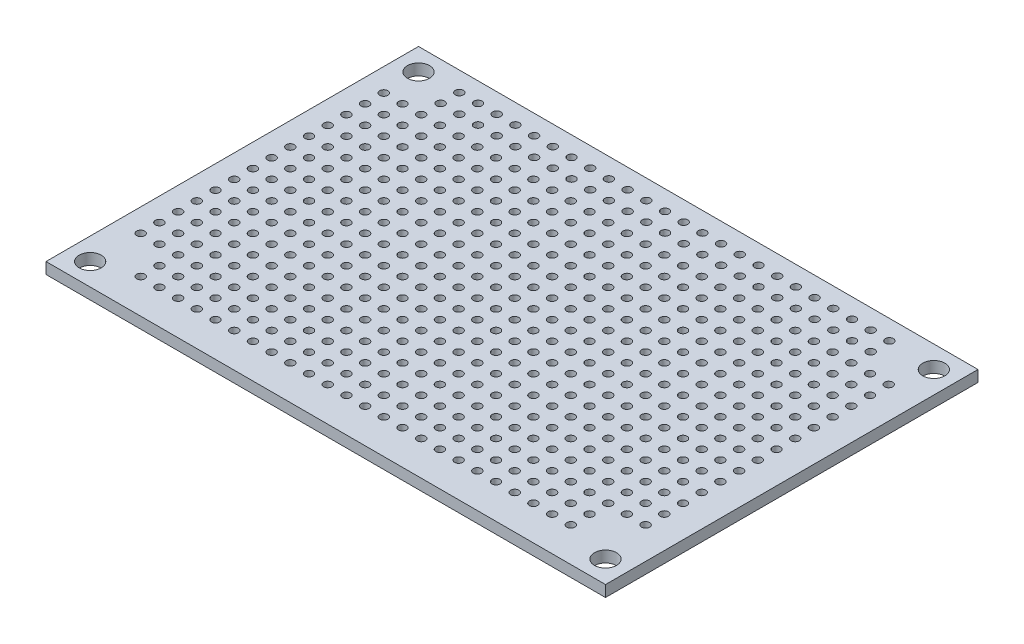
SolidWorks part; units mm, degrees
ref_plane "Front Plane" through (0, 0, 0) normal (0, 0, 1) x (1, 0, 0)
ref_plane "Top Plane" through (0, 0, 0) normal (0, 1, 0) x (1, 0, 0)
ref_plane "Right Plane" through (0, 0, 0) normal (1, 0, 0) x (0, 0, -1)
sketch "Sketch1" plane through (0, 0, 0) normal (0, 1, 0) x (1, 0, 0)
  line L0 (0, 22.3) -> (0, -22.3) construction
  line L1 (-38, -25.3) -> (38, -25.3)
  line L2 (-38, -25.3) -> (-38, 25.3)
  line L3 (-38, 25.3) -> (38, 25.3)
  line L4 (38, -25.3) -> (38, 25.3)
  line L5 (-38, -25.3) -> (38, 25.3) construction
  line L6 (-38, 25.3) -> (38, -25.3) construction
  line L7 (-35, 22.3) -> (35, 22.3) construction
  line L8 (-35, 22.3) -> (-35, -22.3) construction
  line L9 (-35, -22.3) -> (35, -22.3) construction
  line L10 (35, 22.3) -> (35, -22.3) construction
  circle A0 centre (35, 22.3) radius 1.5
  circle A1 centre (35, -22.3) radius 1.5
  circle A2 centre (-35, -22.3) radius 1.5
  circle A3 centre (-35, 22.3) radius 1.5
  point P0 (0, 0)
  dimension "D4" = 3
  dimension "D1" = 76
  dimension "D2" = 50.6
  dimension "D3" = 44.6
  dimension "D5" = 70
extrude "Boss-Extrude1" add sketch "Sketch1" along normal blind 1.53
sketch "Sketch2" plane through (0, 1.53, 0) normal (0, 1, 0) x (1, 0, 0)
  line L0 (-34.8792, 17.4666) -> (-32.3392, 17.4666) construction
  line L1 (-29.7992, 20.1014) -> (-29.7992, 17.5614) construction
  line L2 (-29.7992, -15.5534) -> (-29.7992, -18.0934) construction
  circle A0 centre (-34.8792, 17.4666) radius 0.55
  circle A1 centre (-32.3392, 17.4666) radius 0.55
  circle A2 centre (-29.7992, 17.4666) radius 0.55
  circle A3 centre (-27.2592, 17.4666) radius 0.55
  circle A4 centre (-24.7192, 17.4666) radius 0.55
  circle A5 centre (-22.1792, 17.4666) radius 0.55
  circle A6 centre (-19.6392, 17.4666) radius 0.55
  circle A7 centre (-17.0992, 17.4666) radius 0.55
  circle A8 centre (-14.5592, 17.4666) radius 0.55
  circle A9 centre (-12.0192, 17.4666) radius 0.55
  circle A10 centre (-9.4792, 17.4666) radius 0.55
  circle A11 centre (-6.9392, 17.4666) radius 0.55
  circle A12 centre (-4.3992, 17.4666) radius 0.55
  circle A13 centre (-1.8592, 17.4666) radius 0.55
  circle A14 centre (0.6808, 17.4666) radius 0.55
  circle A15 centre (3.2208, 17.4666) radius 0.55
  circle A16 centre (5.7608, 17.4666) radius 0.55
  circle A17 centre (8.3008, 17.4666) radius 0.55
  circle A18 centre (10.8408, 17.4666) radius 0.55
  circle A19 centre (13.3808, 17.4666) radius 0.55
  circle A20 centre (15.9208, 17.4666) radius 0.55
  circle A21 centre (18.4608, 17.4666) radius 0.55
  circle A22 centre (21.0008, 17.4666) radius 0.55
  circle A23 centre (23.5408, 17.4666) radius 0.55
  circle A24 centre (26.0808, 17.4666) radius 0.55
  circle A25 centre (28.6208, 17.4666) radius 0.55
  circle A26 centre (31.1608, 17.4666) radius 0.55
  circle A27 centre (33.7008, 17.4666) radius 0.55
  circle A28 centre (-32.3392, 14.9266) radius 0.55
  circle A29 centre (-29.7992, 14.9266) radius 0.55
  circle A30 centre (-27.2592, 14.9266) radius 0.55
  circle A31 centre (-24.7192, 14.9266) radius 0.55
  circle A32 centre (-22.1792, 14.9266) radius 0.55
  circle A33 centre (-19.6392, 14.9266) radius 0.55
  circle A34 centre (-17.0992, 14.9266) radius 0.55
  circle A35 centre (-14.5592, 14.9266) radius 0.55
  circle A36 centre (-12.0192, 14.9266) radius 0.55
  circle A37 centre (-9.4792, 14.9266) radius 0.55
  circle A38 centre (-6.9392, 14.9266) radius 0.55
  circle A39 centre (-4.3992, 14.9266) radius 0.55
  circle A40 centre (-1.8592, 14.9266) radius 0.55
  circle A41 centre (0.6808, 14.9266) radius 0.55
  circle A42 centre (3.2208, 14.9266) radius 0.55
  circle A43 centre (5.7608, 14.9266) radius 0.55
  circle A44 centre (8.3008, 14.9266) radius 0.55
  circle A45 centre (10.8408, 14.9266) radius 0.55
  circle A46 centre (13.3808, 14.9266) radius 0.55
  circle A47 centre (15.9208, 14.9266) radius 0.55
  circle A48 centre (18.4608, 14.9266) radius 0.55
  circle A49 centre (21.0008, 14.9266) radius 0.55
  circle A50 centre (23.5408, 14.9266) radius 0.55
  circle A51 centre (26.0808, 14.9266) radius 0.55
  circle A52 centre (28.6208, 14.9266) radius 0.55
  circle A53 centre (31.1608, 14.9266) radius 0.55
  circle A54 centre (33.7008, 14.9266) radius 0.55
  circle A55 centre (-32.3392, 12.3866) radius 0.55
  circle A56 centre (-29.7992, 12.3866) radius 0.55
  circle A57 centre (-27.2592, 12.3866) radius 0.55
  circle A58 centre (-24.7192, 12.3866) radius 0.55
  circle A59 centre (-22.1792, 12.3866) radius 0.55
  circle A60 centre (-19.6392, 12.3866) radius 0.55
  circle A61 centre (-17.0992, 12.3866) radius 0.55
  circle A62 centre (-14.5592, 12.3866) radius 0.55
  circle A63 centre (-12.0192, 12.3866) radius 0.55
  circle A64 centre (-9.4792, 12.3866) radius 0.55
  circle A65 centre (-6.9392, 12.3866) radius 0.55
  circle A66 centre (-4.3992, 12.3866) radius 0.55
  circle A67 centre (-1.8592, 12.3866) radius 0.55
  circle A68 centre (0.6808, 12.3866) radius 0.55
  circle A69 centre (3.2208, 12.3866) radius 0.55
  circle A70 centre (5.7608, 12.3866) radius 0.55
  circle A71 centre (8.3008, 12.3866) radius 0.55
  circle A72 centre (10.8408, 12.3866) radius 0.55
  circle A73 centre (13.3808, 12.3866) radius 0.55
  circle A74 centre (15.9208, 12.3866) radius 0.55
  circle A75 centre (18.4608, 12.3866) radius 0.55
  circle A76 centre (21.0008, 12.3866) radius 0.55
  circle A77 centre (23.5408, 12.3866) radius 0.55
  circle A78 centre (26.0808, 12.3866) radius 0.55
  circle A79 centre (28.6208, 12.3866) radius 0.55
  circle A80 centre (31.1608, 12.3866) radius 0.55
  circle A81 centre (33.7008, 12.3866) radius 0.55
  circle A82 centre (-32.3392, 9.8466) radius 0.55
  circle A83 centre (-29.7992, 9.8466) radius 0.55
  circle A84 centre (-27.2592, 9.8466) radius 0.55
  circle A85 centre (-24.7192, 9.8466) radius 0.55
  circle A86 centre (-22.1792, 9.8466) radius 0.55
  circle A87 centre (-19.6392, 9.8466) radius 0.55
  circle A88 centre (-17.0992, 9.8466) radius 0.55
  circle A89 centre (-14.5592, 9.8466) radius 0.55
  circle A90 centre (-12.0192, 9.8466) radius 0.55
  circle A91 centre (-9.4792, 9.8466) radius 0.55
  circle A92 centre (-6.9392, 9.8466) radius 0.55
  circle A93 centre (-4.3992, 9.8466) radius 0.55
  circle A94 centre (-1.8592, 9.8466) radius 0.55
  circle A95 centre (0.6808, 9.8466) radius 0.55
  circle A96 centre (3.2208, 9.8466) radius 0.55
  circle A97 centre (5.7608, 9.8466) radius 0.55
  circle A98 centre (8.3008, 9.8466) radius 0.55
  circle A99 centre (10.8408, 9.8466) radius 0.55
  circle A100 centre (13.3808, 9.8466) radius 0.55
  circle A101 centre (15.9208, 9.8466) radius 0.55
  circle A102 centre (18.4608, 9.8466) radius 0.55
  circle A103 centre (21.0008, 9.8466) radius 0.55
  circle A104 centre (23.5408, 9.8466) radius 0.55
  circle A105 centre (26.0808, 9.8466) radius 0.55
  circle A106 centre (28.6208, 9.8466) radius 0.55
  circle A107 centre (31.1608, 9.8466) radius 0.55
  circle A108 centre (33.7008, 9.8466) radius 0.55
  circle A109 centre (-32.3392, 7.3066) radius 0.55
  circle A110 centre (-29.7992, 7.3066) radius 0.55
  circle A111 centre (-27.2592, 7.3066) radius 0.55
  circle A112 centre (-24.7192, 7.3066) radius 0.55
  circle A113 centre (-22.1792, 7.3066) radius 0.55
  circle A114 centre (-19.6392, 7.3066) radius 0.55
  circle A115 centre (-17.0992, 7.3066) radius 0.55
  circle A116 centre (-14.5592, 7.3066) radius 0.55
  circle A117 centre (-12.0192, 7.3066) radius 0.55
  circle A118 centre (-9.4792, 7.3066) radius 0.55
  circle A119 centre (-6.9392, 7.3066) radius 0.55
  circle A120 centre (-4.3992, 7.3066) radius 0.55
  circle A121 centre (-1.8592, 7.3066) radius 0.55
  circle A122 centre (0.6808, 7.3066) radius 0.55
  circle A123 centre (3.2208, 7.3066) radius 0.55
  circle A124 centre (5.7608, 7.3066) radius 0.55
  circle A125 centre (8.3008, 7.3066) radius 0.55
  circle A126 centre (10.8408, 7.3066) radius 0.55
  circle A127 centre (13.3808, 7.3066) radius 0.55
  circle A128 centre (15.9208, 7.3066) radius 0.55
  circle A129 centre (18.4608, 7.3066) radius 0.55
  circle A130 centre (21.0008, 7.3066) radius 0.55
  circle A131 centre (23.5408, 7.3066) radius 0.55
  circle A132 centre (26.0808, 7.3066) radius 0.55
  circle A133 centre (28.6208, 7.3066) radius 0.55
  circle A134 centre (31.1608, 7.3066) radius 0.55
  circle A135 centre (33.7008, 7.3066) radius 0.55
  circle A136 centre (-32.3392, 4.7666) radius 0.55
  circle A137 centre (-29.7992, 4.7666) radius 0.55
  circle A138 centre (-27.2592, 4.7666) radius 0.55
  circle A139 centre (-24.7192, 4.7666) radius 0.55
  circle A140 centre (-22.1792, 4.7666) radius 0.55
  circle A141 centre (-19.6392, 4.7666) radius 0.55
  circle A142 centre (-17.0992, 4.7666) radius 0.55
  circle A143 centre (-14.5592, 4.7666) radius 0.55
  circle A144 centre (-12.0192, 4.7666) radius 0.55
  circle A145 centre (-9.4792, 4.7666) radius 0.55
  circle A146 centre (-6.9392, 4.7666) radius 0.55
  circle A147 centre (-4.3992, 4.7666) radius 0.55
  circle A148 centre (-1.8592, 4.7666) radius 0.55
  circle A149 centre (0.6808, 4.7666) radius 0.55
  circle A150 centre (3.2208, 4.7666) radius 0.55
  circle A151 centre (5.7608, 4.7666) radius 0.55
  circle A152 centre (8.3008, 4.7666) radius 0.55
  circle A153 centre (10.8408, 4.7666) radius 0.55
  circle A154 centre (13.3808, 4.7666) radius 0.55
  circle A155 centre (15.9208, 4.7666) radius 0.55
  circle A156 centre (18.4608, 4.7666) radius 0.55
  circle A157 centre (21.0008, 4.7666) radius 0.55
  circle A158 centre (23.5408, 4.7666) radius 0.55
  circle A159 centre (26.0808, 4.7666) radius 0.55
  circle A160 centre (28.6208, 4.7666) radius 0.55
  circle A161 centre (31.1608, 4.7666) radius 0.55
  circle A162 centre (33.7008, 4.7666) radius 0.55
  circle A163 centre (-32.3392, 2.2266) radius 0.55
  circle A164 centre (-29.7992, 2.2266) radius 0.55
  circle A165 centre (-27.2592, 2.2266) radius 0.55
  circle A166 centre (-24.7192, 2.2266) radius 0.55
  circle A167 centre (-22.1792, 2.2266) radius 0.55
  circle A168 centre (-19.6392, 2.2266) radius 0.55
  circle A169 centre (-17.0992, 2.2266) radius 0.55
  circle A170 centre (-14.5592, 2.2266) radius 0.55
  circle A171 centre (-12.0192, 2.2266) radius 0.55
  circle A172 centre (-9.4792, 2.2266) radius 0.55
  circle A173 centre (-6.9392, 2.2266) radius 0.55
  circle A174 centre (-4.3992, 2.2266) radius 0.55
  circle A175 centre (-1.8592, 2.2266) radius 0.55
  circle A176 centre (0.6808, 2.2266) radius 0.55
  circle A177 centre (3.2208, 2.2266) radius 0.55
  circle A178 centre (5.7608, 2.2266) radius 0.55
  circle A179 centre (8.3008, 2.2266) radius 0.55
  circle A180 centre (10.8408, 2.2266) radius 0.55
  circle A181 centre (13.3808, 2.2266) radius 0.55
  circle A182 centre (15.9208, 2.2266) radius 0.55
  circle A183 centre (18.4608, 2.2266) radius 0.55
  circle A184 centre (21.0008, 2.2266) radius 0.55
  circle A185 centre (23.5408, 2.2266) radius 0.55
  circle A186 centre (26.0808, 2.2266) radius 0.55
  circle A187 centre (28.6208, 2.2266) radius 0.55
  circle A188 centre (31.1608, 2.2266) radius 0.55
  circle A189 centre (33.7008, 2.2266) radius 0.55
  circle A190 centre (-32.3392, -0.3134) radius 0.55
  circle A191 centre (-29.7992, -0.3134) radius 0.55
  circle A192 centre (-27.2592, -0.3134) radius 0.55
  circle A193 centre (-24.7192, -0.3134) radius 0.55
  circle A194 centre (-22.1792, -0.3134) radius 0.55
  circle A195 centre (-19.6392, -0.3134) radius 0.55
  circle A196 centre (-17.0992, -0.3134) radius 0.55
  circle A197 centre (-14.5592, -0.3134) radius 0.55
  circle A198 centre (-12.0192, -0.3134) radius 0.55
  circle A199 centre (-9.4792, -0.3134) radius 0.55
  circle A200 centre (-6.9392, -0.3134) radius 0.55
  circle A201 centre (-4.3992, -0.3134) radius 0.55
  circle A202 centre (-1.8592, -0.3134) radius 0.55
  circle A203 centre (0.6808, -0.3134) radius 0.55
  circle A204 centre (3.2208, -0.3134) radius 0.55
  circle A205 centre (5.7608, -0.3134) radius 0.55
  circle A206 centre (8.3008, -0.3134) radius 0.55
  circle A207 centre (10.8408, -0.3134) radius 0.55
  circle A208 centre (13.3808, -0.3134) radius 0.55
  circle A209 centre (15.9208, -0.3134) radius 0.55
  circle A210 centre (18.4608, -0.3134) radius 0.55
  circle A211 centre (21.0008, -0.3134) radius 0.55
  circle A212 centre (23.5408, -0.3134) radius 0.55
  circle A213 centre (26.0808, -0.3134) radius 0.55
  circle A214 centre (28.6208, -0.3134) radius 0.55
  circle A215 centre (31.1608, -0.3134) radius 0.55
  circle A216 centre (33.7008, -0.3134) radius 0.55
  circle A217 centre (-32.3392, -2.8534) radius 0.55
  circle A218 centre (-29.7992, -2.8534) radius 0.55
  circle A219 centre (-27.2592, -2.8534) radius 0.55
  circle A220 centre (-24.7192, -2.8534) radius 0.55
  circle A221 centre (-22.1792, -2.8534) radius 0.55
  circle A222 centre (-19.6392, -2.8534) radius 0.55
  circle A223 centre (-17.0992, -2.8534) radius 0.55
  circle A224 centre (-14.5592, -2.8534) radius 0.55
  circle A225 centre (-12.0192, -2.8534) radius 0.55
  circle A226 centre (-9.4792, -2.8534) radius 0.55
  circle A227 centre (-6.9392, -2.8534) radius 0.55
  circle A228 centre (-4.3992, -2.8534) radius 0.55
  circle A229 centre (-1.8592, -2.8534) radius 0.55
  circle A230 centre (0.6808, -2.8534) radius 0.55
  circle A231 centre (3.2208, -2.8534) radius 0.55
  circle A232 centre (5.7608, -2.8534) radius 0.55
  circle A233 centre (8.3008, -2.8534) radius 0.55
  circle A234 centre (10.8408, -2.8534) radius 0.55
  circle A235 centre (13.3808, -2.8534) radius 0.55
  circle A236 centre (15.9208, -2.8534) radius 0.55
  circle A237 centre (18.4608, -2.8534) radius 0.55
  circle A238 centre (21.0008, -2.8534) radius 0.55
  circle A239 centre (23.5408, -2.8534) radius 0.55
  circle A240 centre (26.0808, -2.8534) radius 0.55
  circle A241 centre (28.6208, -2.8534) radius 0.55
  circle A242 centre (31.1608, -2.8534) radius 0.55
  circle A243 centre (33.7008, -2.8534) radius 0.55
  circle A244 centre (-32.3392, -5.3934) radius 0.55
  circle A245 centre (-29.7992, -5.3934) radius 0.55
  circle A246 centre (-27.2592, -5.3934) radius 0.55
  circle A247 centre (-24.7192, -5.3934) radius 0.55
  circle A248 centre (-22.1792, -5.3934) radius 0.55
  circle A249 centre (-19.6392, -5.3934) radius 0.55
  circle A250 centre (-17.0992, -5.3934) radius 0.55
  circle A251 centre (-14.5592, -5.3934) radius 0.55
  circle A252 centre (-12.0192, -5.3934) radius 0.55
  circle A253 centre (-9.4792, -5.3934) radius 0.55
  circle A254 centre (-6.9392, -5.3934) radius 0.55
  circle A255 centre (-4.3992, -5.3934) radius 0.55
  circle A256 centre (-1.8592, -5.3934) radius 0.55
  circle A257 centre (0.6808, -5.3934) radius 0.55
  circle A258 centre (3.2208, -5.3934) radius 0.55
  circle A259 centre (5.7608, -5.3934) radius 0.55
  circle A260 centre (8.3008, -5.3934) radius 0.55
  circle A261 centre (10.8408, -5.3934) radius 0.55
  circle A262 centre (13.3808, -5.3934) radius 0.55
  circle A263 centre (15.9208, -5.3934) radius 0.55
  circle A264 centre (18.4608, -5.3934) radius 0.55
  circle A265 centre (21.0008, -5.3934) radius 0.55
  circle A266 centre (23.5408, -5.3934) radius 0.55
  circle A267 centre (26.0808, -5.3934) radius 0.55
  circle A268 centre (28.6208, -5.3934) radius 0.55
  circle A269 centre (31.1608, -5.3934) radius 0.55
  circle A270 centre (33.7008, -5.3934) radius 0.55
  circle A271 centre (-32.3392, -7.9334) radius 0.55
  circle A272 centre (-29.7992, -7.9334) radius 0.55
  circle A273 centre (-27.2592, -7.9334) radius 0.55
  circle A274 centre (-24.7192, -7.9334) radius 0.55
  circle A275 centre (-22.1792, -7.9334) radius 0.55
  circle A276 centre (-19.6392, -7.9334) radius 0.55
  circle A277 centre (-17.0992, -7.9334) radius 0.55
  circle A278 centre (-14.5592, -7.9334) radius 0.55
  circle A279 centre (-12.0192, -7.9334) radius 0.55
  circle A280 centre (-9.4792, -7.9334) radius 0.55
  circle A281 centre (-6.9392, -7.9334) radius 0.55
  circle A282 centre (-4.3992, -7.9334) radius 0.55
  circle A283 centre (-1.8592, -7.9334) radius 0.55
  circle A284 centre (0.6808, -7.9334) radius 0.55
  circle A285 centre (3.2208, -7.9334) radius 0.55
  circle A286 centre (5.7608, -7.9334) radius 0.55
  circle A287 centre (8.3008, -7.9334) radius 0.55
  circle A288 centre (10.8408, -7.9334) radius 0.55
  circle A289 centre (13.3808, -7.9334) radius 0.55
  circle A290 centre (15.9208, -7.9334) radius 0.55
  circle A291 centre (18.4608, -7.9334) radius 0.55
  circle A292 centre (21.0008, -7.9334) radius 0.55
  circle A293 centre (23.5408, -7.9334) radius 0.55
  circle A294 centre (26.0808, -7.9334) radius 0.55
  circle A295 centre (28.6208, -7.9334) radius 0.55
  circle A296 centre (31.1608, -7.9334) radius 0.55
  circle A297 centre (33.7008, -7.9334) radius 0.55
  circle A298 centre (-32.3392, -10.4734) radius 0.55
  circle A299 centre (-29.7992, -10.4734) radius 0.55
  circle A300 centre (-27.2592, -10.4734) radius 0.55
  circle A301 centre (-24.7192, -10.4734) radius 0.55
  circle A302 centre (-22.1792, -10.4734) radius 0.55
  circle A303 centre (-19.6392, -10.4734) radius 0.55
  circle A304 centre (-17.0992, -10.4734) radius 0.55
  circle A305 centre (-14.5592, -10.4734) radius 0.55
  circle A306 centre (-12.0192, -10.4734) radius 0.55
  circle A307 centre (-9.4792, -10.4734) radius 0.55
  circle A308 centre (-6.9392, -10.4734) radius 0.55
  circle A309 centre (-4.3992, -10.4734) radius 0.55
  circle A310 centre (-1.8592, -10.4734) radius 0.55
  circle A311 centre (0.6808, -10.4734) radius 0.55
  circle A312 centre (3.2208, -10.4734) radius 0.55
  circle A313 centre (5.7608, -10.4734) radius 0.55
  circle A314 centre (8.3008, -10.4734) radius 0.55
  circle A315 centre (10.8408, -10.4734) radius 0.55
  circle A316 centre (13.3808, -10.4734) radius 0.55
  circle A317 centre (15.9208, -10.4734) radius 0.55
  circle A318 centre (18.4608, -10.4734) radius 0.55
  circle A319 centre (21.0008, -10.4734) radius 0.55
  circle A320 centre (23.5408, -10.4734) radius 0.55
  circle A321 centre (26.0808, -10.4734) radius 0.55
  circle A322 centre (28.6208, -10.4734) radius 0.55
  circle A323 centre (31.1608, -10.4734) radius 0.55
  circle A324 centre (33.7008, -10.4734) radius 0.55
  circle A325 centre (-32.3392, -13.0134) radius 0.55
  circle A326 centre (-29.7992, -13.0134) radius 0.55
  circle A327 centre (-27.2592, -13.0134) radius 0.55
  circle A328 centre (-24.7192, -13.0134) radius 0.55
  circle A329 centre (-22.1792, -13.0134) radius 0.55
  circle A330 centre (-19.6392, -13.0134) radius 0.55
  circle A331 centre (-17.0992, -13.0134) radius 0.55
  circle A332 centre (-14.5592, -13.0134) radius 0.55
  circle A333 centre (-12.0192, -13.0134) radius 0.55
  circle A334 centre (-9.4792, -13.0134) radius 0.55
  circle A335 centre (-6.9392, -13.0134) radius 0.55
  circle A336 centre (-4.3992, -13.0134) radius 0.55
  circle A337 centre (-1.8592, -13.0134) radius 0.55
  circle A338 centre (0.6808, -13.0134) radius 0.55
  circle A339 centre (3.2208, -13.0134) radius 0.55
  circle A340 centre (5.7608, -13.0134) radius 0.55
  circle A341 centre (8.3008, -13.0134) radius 0.55
  circle A342 centre (10.8408, -13.0134) radius 0.55
  circle A343 centre (13.3808, -13.0134) radius 0.55
  circle A344 centre (15.9208, -13.0134) radius 0.55
  circle A345 centre (18.4608, -13.0134) radius 0.55
  circle A346 centre (21.0008, -13.0134) radius 0.55
  circle A347 centre (23.5408, -13.0134) radius 0.55
  circle A348 centre (26.0808, -13.0134) radius 0.55
  circle A349 centre (28.6208, -13.0134) radius 0.55
  circle A350 centre (31.1608, -13.0134) radius 0.55
  circle A351 centre (33.7008, -13.0134) radius 0.55
  circle A352 centre (-32.3392, -15.5534) radius 0.55
  circle A353 centre (-29.7992, -15.5534) radius 0.55
  circle A354 centre (-27.2592, -15.5534) radius 0.55
  circle A355 centre (-24.7192, -15.5534) radius 0.55
  circle A356 centre (-22.1792, -15.5534) radius 0.55
  circle A357 centre (-19.6392, -15.5534) radius 0.55
  circle A358 centre (-17.0992, -15.5534) radius 0.55
  circle A359 centre (-14.5592, -15.5534) radius 0.55
  circle A360 centre (-12.0192, -15.5534) radius 0.55
  circle A361 centre (-9.4792, -15.5534) radius 0.55
  circle A362 centre (-6.9392, -15.5534) radius 0.55
  circle A363 centre (-4.3992, -15.5534) radius 0.55
  circle A364 centre (-1.8592, -15.5534) radius 0.55
  circle A365 centre (0.6808, -15.5534) radius 0.55
  circle A366 centre (3.2208, -15.5534) radius 0.55
  circle A367 centre (5.7608, -15.5534) radius 0.55
  circle A368 centre (8.3008, -15.5534) radius 0.55
  circle A369 centre (10.8408, -15.5534) radius 0.55
  circle A370 centre (13.3808, -15.5534) radius 0.55
  circle A371 centre (15.9208, -15.5534) radius 0.55
  circle A372 centre (18.4608, -15.5534) radius 0.55
  circle A373 centre (21.0008, -15.5534) radius 0.55
  circle A374 centre (23.5408, -15.5534) radius 0.55
  circle A375 centre (26.0808, -15.5534) radius 0.55
  circle A376 centre (28.6208, -15.5534) radius 0.55
  circle A377 centre (31.1608, -15.5534) radius 0.55
  circle A378 centre (33.7008, -15.5534) radius 0.55
  circle A379 centre (-34.8792, 14.9266) radius 0.55
  circle A380 centre (-34.8792, 12.3866) radius 0.55
  circle A381 centre (-34.8792, 9.8466) radius 0.55
  circle A382 centre (-34.8792, 7.3066) radius 0.55
  circle A383 centre (-34.8792, 4.7666) radius 0.55
  circle A384 centre (-34.8792, 2.2266) radius 0.55
  circle A385 centre (-34.8792, -0.3134) radius 0.55
  circle A386 centre (-34.8792, -2.8534) radius 0.55
  circle A387 centre (-34.8792, -5.3934) radius 0.55
  circle A388 centre (-34.8792, -7.9334) radius 0.55
  circle A389 centre (-34.8792, -10.4734) radius 0.55
  circle A390 centre (-34.8792, -13.0134) radius 0.55
  circle A391 centre (-34.8792, -15.5534) radius 0.55
  circle A392 centre (-29.7992, 20.1014) radius 0.55
  circle A393 centre (-27.2592, 20.1014) radius 0.55
  circle A394 centre (-24.7192, 20.1014) radius 0.55
  circle A395 centre (-22.1792, 20.1014) radius 0.55
  circle A396 centre (-19.6392, 20.1014) radius 0.55
  circle A397 centre (-17.0992, 20.1014) radius 0.55
  circle A398 centre (-14.5592, 20.1014) radius 0.55
  circle A399 centre (-12.0192, 20.1014) radius 0.55
  circle A400 centre (-9.4792, 20.1014) radius 0.55
  circle A401 centre (-6.9392, 20.1014) radius 0.55
  circle A402 centre (-4.3992, 20.1014) radius 0.55
  circle A403 centre (-1.8592, 20.1014) radius 0.55
  circle A404 centre (0.6808, 20.1014) radius 0.55
  circle A405 centre (3.2208, 20.1014) radius 0.55
  circle A406 centre (5.7608, 20.1014) radius 0.55
  circle A407 centre (8.3008, 20.1014) radius 0.55
  circle A408 centre (10.8408, 20.1014) radius 0.55
  circle A409 centre (13.3808, 20.1014) radius 0.55
  circle A410 centre (15.9208, 20.1014) radius 0.55
  circle A411 centre (18.4608, 20.1014) radius 0.55
  circle A412 centre (21.0008, 20.1014) radius 0.55
  circle A413 centre (23.5408, 20.1014) radius 0.55
  circle A414 centre (26.0808, 20.1014) radius 0.55
  circle A415 centre (28.6208, 20.1014) radius 0.55
  circle A416 centre (-27.2592, 22.6414) radius 0.55
  circle A417 centre (-24.7192, 22.6414) radius 0.55
  circle A418 centre (-22.1792, 22.6414) radius 0.55
  circle A419 centre (-19.6392, 22.6414) radius 0.55
  circle A420 centre (-17.0992, 22.6414) radius 0.55
  circle A421 centre (-14.5592, 22.6414) radius 0.55
  circle A422 centre (-12.0192, 22.6414) radius 0.55
  circle A423 centre (-9.4792, 22.6414) radius 0.55
  circle A424 centre (-6.9392, 22.6414) radius 0.55
  circle A425 centre (-4.3992, 22.6414) radius 0.55
  circle A426 centre (-1.8592, 22.6414) radius 0.55
  circle A427 centre (0.6808, 22.6414) radius 0.55
  circle A428 centre (3.2208, 22.6414) radius 0.55
  circle A429 centre (5.7608, 22.6414) radius 0.55
  circle A430 centre (8.3008, 22.6414) radius 0.55
  circle A431 centre (10.8408, 22.6414) radius 0.55
  circle A432 centre (13.3808, 22.6414) radius 0.55
  circle A433 centre (15.9208, 22.6414) radius 0.55
  circle A434 centre (18.4608, 22.6414) radius 0.55
  circle A435 centre (21.0008, 22.6414) radius 0.55
  circle A436 centre (23.5408, 22.6414) radius 0.55
  circle A437 centre (26.0808, 22.6414) radius 0.55
  circle A438 centre (28.6208, 22.6414) radius 0.55
  circle A439 centre (-29.7992, 22.6414) radius 0.55
  circle A440 centre (-29.7992, -18.0934) radius 0.55
  circle A441 centre (-27.2592, -18.0934) radius 0.55
  circle A442 centre (-24.7192, -18.0934) radius 0.55
  circle A443 centre (-22.1792, -18.0934) radius 0.55
  circle A444 centre (-19.6392, -18.0934) radius 0.55
  circle A445 centre (-17.0992, -18.0934) radius 0.55
  circle A446 centre (-14.5592, -18.0934) radius 0.55
  circle A447 centre (-12.0192, -18.0934) radius 0.55
  circle A448 centre (-9.4792, -18.0934) radius 0.55
  circle A449 centre (-6.9392, -18.0934) radius 0.55
  circle A450 centre (-4.3992, -18.0934) radius 0.55
  circle A451 centre (-1.8592, -18.0934) radius 0.55
  circle A452 centre (0.6808, -18.0934) radius 0.55
  circle A453 centre (3.2208, -18.0934) radius 0.55
  circle A454 centre (5.7608, -18.0934) radius 0.55
  circle A455 centre (8.3008, -18.0934) radius 0.55
  circle A456 centre (10.8408, -18.0934) radius 0.55
  circle A457 centre (13.3808, -18.0934) radius 0.55
  circle A458 centre (15.9208, -18.0934) radius 0.55
  circle A459 centre (18.4608, -18.0934) radius 0.55
  circle A460 centre (21.0008, -18.0934) radius 0.55
  circle A461 centre (23.5408, -18.0934) radius 0.55
  circle A462 centre (26.0808, -18.0934) radius 0.55
  circle A463 centre (28.6208, -18.0934) radius 0.55
  circle A464 centre (-27.2592, -20.6334) radius 0.55
  circle A465 centre (-24.7192, -20.6334) radius 0.55
  circle A466 centre (-22.1792, -20.6334) radius 0.55
  circle A467 centre (-19.6392, -20.6334) radius 0.55
  circle A468 centre (-17.0992, -20.6334) radius 0.55
  circle A469 centre (-14.5592, -20.6334) radius 0.55
  circle A470 centre (-12.0192, -20.6334) radius 0.55
  circle A471 centre (-9.4792, -20.6334) radius 0.55
  circle A472 centre (-6.9392, -20.6334) radius 0.55
  circle A473 centre (-4.3992, -20.6334) radius 0.55
  circle A474 centre (-1.8592, -20.6334) radius 0.55
  circle A475 centre (0.6808, -20.6334) radius 0.55
  circle A476 centre (3.2208, -20.6334) radius 0.55
  circle A477 centre (5.7608, -20.6334) radius 0.55
  circle A478 centre (8.3008, -20.6334) radius 0.55
  circle A479 centre (10.8408, -20.6334) radius 0.55
  circle A480 centre (13.3808, -20.6334) radius 0.55
  circle A481 centre (15.9208, -20.6334) radius 0.55
  circle A482 centre (18.4608, -20.6334) radius 0.55
  circle A483 centre (21.0008, -20.6334) radius 0.55
  circle A484 centre (23.5408, -20.6334) radius 0.55
  circle A485 centre (26.0808, -20.6334) radius 0.55
  circle A486 centre (28.6208, -20.6334) radius 0.55
  circle A487 centre (-29.7992, -20.6334) radius 0.55
  dimension "D3" = 1.1
  dimension "D1" = 28
  dimension "D2" = 14
  dimension "D4" = 24
  dimension "D5" = 2
  dimension "D6" = 24
  dimension "D7" = 2
extrude "Cut-Extrude1" cut sketch "Sketch2" against normal through all
